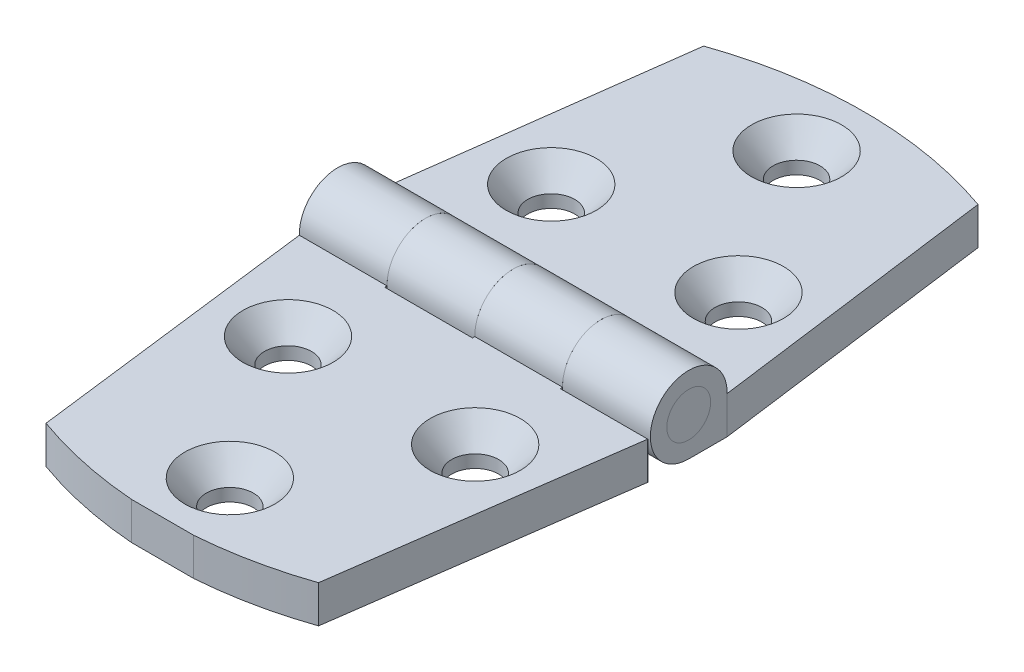
SolidWorks part; units mm, degrees
ref_plane "Front" through (0, 0, 0) normal (0, 0, 1) x (1, 0, 0)
ref_plane "Top" through (0, 0, 0) normal (0, 1, 0) x (1, 0, 0)
ref_plane "Right" through (0, 0, 0) normal (1, 0, 0) x (0, 0, -1)
sketch "Sketch1" plane through (0, 0, 0) normal (1, 0, 0) x (0, 0, -1)
  line L0 (-38.1, -0.1032) -> (-4.1659, -0.1032)
  line L3 (0, -4.1672) -> (-38.1, -4.1672)
  line L4 (-38.1, -0.1032) -> (-38.1, -4.1672)
  line L6 (-38.1, -4.1672) -> (38.1, -4.1672) construction
  circle A0 centre (0, 0) radius 2.3813
  arc A2 (-4.1659, -0.1032) -> (0, -4.1672) centre (0, 0) cw
  dimension "D1" = 8.3344
  dimension "Pin Dia" = 4.7625
  dimension "Th" = 4.064
  dimension "Open Wd" = 76.2
extrude "Left Leaf" add sketch "Sketch1" along normal mid plane 38.1
sketch "Sketch2" plane through (0, 0, 0) normal (0, 1, 0) x (1, 0, 0)
  line L0 (19.05, 4.1672) -> (-19.05, 4.1672) construction
  line L3 (-19.05, 4.1672) -> (-9.525, 4.1672) construction
  line L4 (-19.05, 4.1672) -> (-19.05, -7.8214) construction
  line L5 (19.05, -4.1659) -> (19.05, -38.1) construction
  line L6 (-9.525, -4.4212) -> (0, -4.4212)
  line L7 (9.525, 4.1672) -> (19.05, 4.1672)
  line L8 (-9.525, 4.1672) -> (0, 4.1672)
  line L9 (-9.525, 4.1672) -> (-9.525, -4.4212)
  line L10 (-19.05, -4.1672) -> (19.05, -4.1672) construction
  line L11 (9.525, 4.1672) -> (9.525, -4.4212)
  line L12 (0, 4.1672) -> (9.525, 4.1672) construction
  line L13 (9.525, -4.4212) -> (19.05, -4.4212)
  line L14 (0, 4.1672) -> (0, -4.4212)
  line L17 (19.05, 4.1672) -> (19.05, -4.4212)
  dimension "D1" = 0.254
extrude "Cut-Extrude1" cut sketch "Sketch2" against normal through all and the other way through all
sketch "Sketch3" plane through (0, 0, 0) normal (1, 0, 0) x (0, 0, -1)
  line L0 (0, 17.042) -> (0, -15.7543) construction
  line L1 (38.1, -0.1032) -> (38.1, -4.1672)
  line L2 (-38.1, -4.1672) -> (38.1, -4.1672) construction
  line L4 (4.1659, -0.1032) -> (38.1, -0.1032)
  line L5 (-38.1, -0.1032) -> (-4.1659, -0.1032) construction
  line L8 (0, -4.1672) -> (-38.1, -4.1672) construction
  line L19 (0, -4.1672) -> (38.1, -4.1672)
  circle A1 centre (0, 0) radius 2.3813 construction
  arc A4 (4.1659, -0.1032) -> (0, -4.1672) centre (0, 0) ccw
  circle A5 centre (0, 0) radius 2.3813
extrude "Right Leaf" add sketch "Sketch3" along normal mid plane 38.1 separate body
sketch "Sketch9" plane through (0, 0, 0) normal (0, 1, 0) x (1, 0, 0)
  line L0 (-19.05, 4.4212) -> (-9.525, 4.4212)
  line L2 (0, 4.4212) -> (0, -4.4212)
  line L3 (0, -4.4212) -> (9.525, -4.4212)
  line L4 (9.525, 4.4212) -> (9.525, -4.4212)
  line L6 (-19.05, 4.4212) -> (-19.05, -4.4212)
  line L7 (-19.05, -4.4212) -> (-9.525, -4.4212)
  line L8 (-9.525, 4.4212) -> (-9.525, -4.4212)
  line L9 (0, 4.4212) -> (9.525, 4.4212)
  line L10 (19.05, 4.1672) -> (-19.05, 4.1672) construction
  line L11 (-19.05, 38.1) -> (-19.05, 4.1659) construction
  dimension "D1" = 0.254
extrude "Cut-Extrude2" cut sketch "Sketch9" against normal through all and the other way through all
sketch "Sketch10" plane through (0, 0, 0) normal (1, 0, 0) x (0, 0, -1)
  circle A0 centre (0, 0) radius 2.3813
  circle A1 centre (0, 0) radius 2.3813 construction
extrude "Extrude1" add sketch "Sketch10" along normal mid plane 38.1 separate body
sketch "Sketch13" plane through (0, -0.1032, 0) normal (0, 1, 0) x (-1, 0, 0)
  line L0 (19.05, 0) -> (-19.05, 0.127) construction
  line L1 (-19.05, -4.1672) -> (-19.05, 4.4212) construction
  line L2 (19.0222, -4.1671) -> (14.8893, -35.56)
  line L3 (14.8893, -35.56) -> (-14.8893, -35.56) construction
  line L4 (-14.8893, -35.56) -> (-19.05, -4.1708)
  line L5 (0, 38.1) -> (0, -38.1) construction
  line L6 (19.05, -38.1) -> (19.05, -4.4212) construction
  line L7 (-19.05, -38.1) -> (19.05, -38.1) construction
  line L8 (19.0222, -4.1671) -> (25.3525, -4.1671)
  line L9 (25.3525, -4.1671) -> (25.3525, -58.5817)
  line L10 (25.3525, -58.5817) -> (-24.2515, -58.5817)
  line L11 (-24.2515, -58.5817) -> (-24.2515, -4.1708)
  line L12 (-24.2515, -4.1708) -> (-19.05, -4.1708)
  line L13 (-23.86, 58.869) -> (-24.2228, 4.4593)
  line L14 (-24.2228, 4.4593) -> (-19.0213, 4.4247)
  line L15 (-14.6514, 35.7855) -> (-19.0213, 4.4247)
  line L16 (25.7429, 58.5384) -> (-23.86, 58.869)
  line L17 (25.3801, 4.125) -> (25.7429, 58.5384)
  line L18 (19.05, 4.1672) -> (25.3801, 4.125)
  line L19 (19.05, 4.1672) -> (15.1264, 35.5869)
  line L20 (-19.05, -38.1) -> (-19.05, -4.1659) construction
  arc A0 (14.8893, -35.56) -> (-14.8893, -35.56) centre (0, 6.8098) cw
  arc A1 (15.1264, 35.5869) -> (-14.6514, 35.7855) centre (-0.045, -6.6827) ccw
  point P8 (0, -35.56)
  dimension "D1" = 7.5
  dimension "D2" = 2.54
extrude "Cut-Extrude3" cut sketch "Sketch13" against normal through all
sketch "Sketch11" plane through (0, -0.1032, 0) normal (0, 1, 0) x (-1, 0, 0)
  line L0 (-19.05, 4.1672) -> (-19.05, -4.1672) construction
  line L6 (0, 38.1) -> (0, -38.1) construction
  line L8 (19.05, 0) -> (-19.05, 0) construction
  line L9 (0, -38.1) -> (0, 38.2271) construction
  arc A0 (-14.8893, -35.56) -> (14.8893, -35.56) centre (0, 6.8098) ccw construction
  arc A1 (15.1264, 35.5869) -> (-14.6514, 35.7855) centre (-0.045, -6.6827) ccw construction
  point P6 (0, -30.7578)
  point P7 (10.16, -14.2875)
  point P10 (-10.16, -14.2875)
  point P11 (0, 30.7578)
  point P12 (10.16, 14.2875)
  point P13 (-10.16, 14.2875)
  dimension "D1" = 28.575
  dimension "D2" = 61.5156
  dimension "D3" = 20.32
hole_wizard "CSK for #10 Flat Head Machine Screw1" positions "3DSketch1" profile "Sketch12" countersink size "#10" standard "Ansi Inch" end condition through all
sketch3d "3DSketch1"
  point P18 (0, -0.1032, -30.7578)
  point P22 (-10.16, -0.1032, -14.2875)
  point P25 (10.16, -0.1032, -14.2875)
  point P28 (-10.16, -0.1032, 14.2875)
  point P31 (10.16, -0.1032, 14.2875)
  point P34 (0, -0.1032, 30.7578)
sketch "Sketch12" plane through (0, -0.1032, -30.7578) normal (1, 0, 0) x (0, 0, 1)
  line L0 (0, 0) -> (0, 4.064)
  line L1 (0, 4.064) -> (2.5527, 4.064)
  line L2 (2.5527, 4.064) -> (2.5527, 2.6882)
  line L3 (2.5527, 2.6882) -> (4.8895, 0)
  line L5 (4.8895, 0) -> (0, 0)
  line L6 (-2.5527, 2.6882) -> (-4.8895, 0) construction
  line L11 (0, -6.35) -> (0, 107.95) construction
  dimension "Thru Hole Dia." = 5.1054
  dimension "Thru Hole Depth" = 4.064
  dimension "Near C'Sink Dia." = 9.779
  dimension "Near C'Sink Angle" = 82
